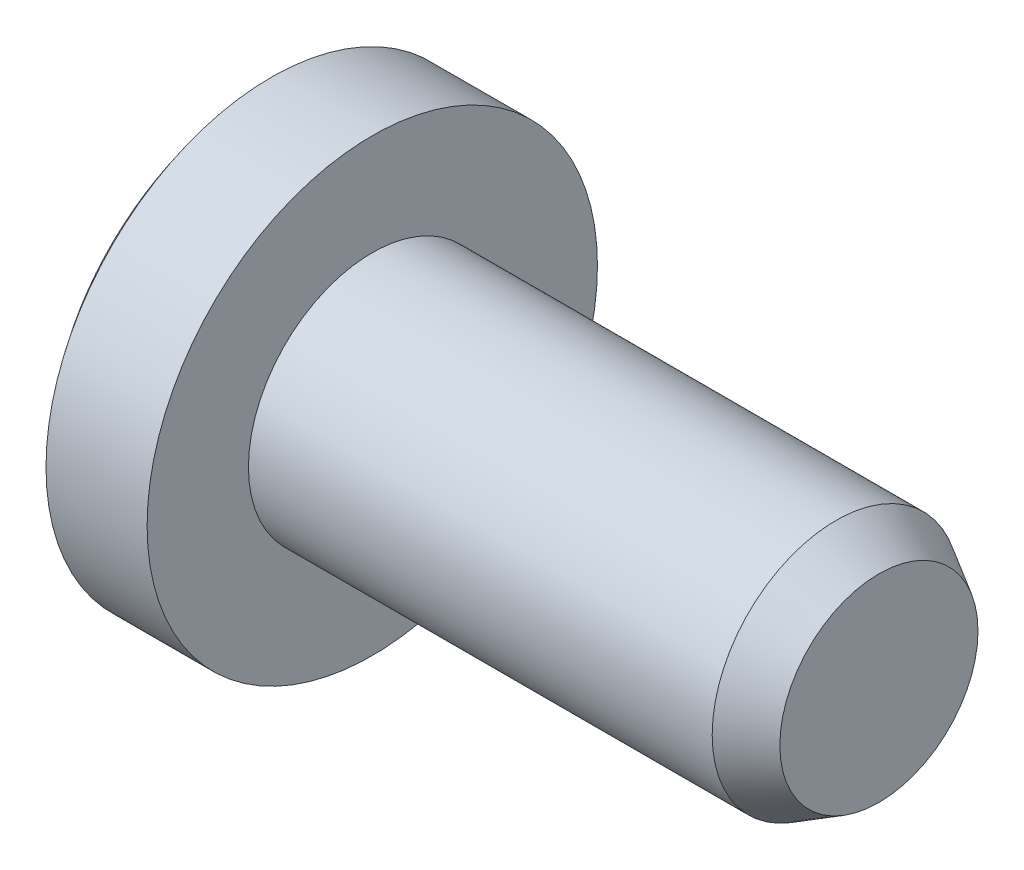
SolidWorks part; units mm, degrees
ref_plane "Front Plane" through (0, 0, 0) normal (0, 0, 1) x (1, 0, 0)
ref_plane "Top Plane" through (0, 0, 0) normal (0, 1, 0) x (1, 0, 0)
ref_plane "Right Plane" through (0, 0, 0) normal (1, 0, 0) x (0, 0, -1)
sketch "Sketch1" plane through (0, 0, 0) normal (0, 0, 1) x (1, 0, 0)
  line L0 (0, 0) -> (5.2282, 0) construction
  line L2 (0, 2) -> (-0.898, 2)
  line L3 (-1.6, 0) -> (-1.6, -0.7496) construction
  line L4 (-1.6, 0) -> (4.5, 0)
  line L5 (0, 1.1) -> (4.5, 1.1)
  line L6 (4.5, 1.1) -> (4.5, 0)
  line L7 (0, 1.1) -> (0, 2)
  arc A0 (-0.898, 2) -> (-1.6, 0) centre (1.6, 0) ccw
  dimension "l" = 4.5
revolve "Revolve1" add sketch "Sketch1" angle 360 about L0
cosmetic thread "ThreadCosmetic" [suppressed] parameters "D1"=4.28, "D2"=1.65
chamfer "Chamfer1" distance 0.22 angle 60 1 edges at (4.5, 0, 1.1) first distance on face at (4.5, 0, 1.1)
sketch "Sketch5" plane through (0, 0, 0) normal (0, 0, 1) x (1, 0, 0)
  line L0 (0.3703, 0.825) -> (0.2069, 0.825)
  line L1 (0.2069, 0.825) -> (0.0481, 1.1)
  line L2 (0.3703, 0.825) -> (0.529, 1.1)
  line L3 (0.0481, 1.1) -> (0.0481, 1.35)
  line L4 (0.529, 1.1) -> (0.529, 1.35)
  line L5 (0.0481, 1.35) -> (0.529, 1.35)
  line L6 (0.2886, 0.825) -> (0.2886, 0) construction
  line L7 (0, 0) -> (7.3035, 0) construction
  line L9 (4.1189, 1.1) -> (0, 1.1) construction
  line L12 (0, -1.1) -> (0, 1.1) construction
  dimension "D2" = 60
  dimension "D3" = 0.25
  dimension "minordia" = 1.65
  dimension "threadstart" = 0.2886
revolve "ThreadSchematic" [suppressed] cut sketch "Sketch5" angle 360 about L7
pattern_linear "ThdSchPat" [suppressed] count 10 spacing 0.4809 along (1, 0, 0) of bodies 105
sketch "Sketch2" plane through (0, 0, 0) normal (0, 0, 1) x (1, 0, 0)
  line L0 (0, 0) -> (5.7679, 0) construction
  line L1 (4.5, 0) -> (2.5947, 1.1)
  line L3 (4.5, 1.1) -> (4.5, 0) construction
  line L4 (2.5947, 1.1) -> (2.5947, 1.2)
  line L5 (2.5947, 1.2) -> (4.6, 1.2)
  line L6 (4.6, 1.2) -> (4.6, 0)
  line L7 (4.6, 0) -> (4.5, 0)
  point P9 (0, 1.1)
  dimension "D1" = 30
  dimension "D2" = 0.1
  dimension "D3" = 0.1
revolve "EndCone" [suppressed] cut sketch "Sketch2" angle 360 about L0
ref_plane "Plane4" through (-1.6, 0, 0) normal (1, 0, 0) x (0, 0, -1)
sketch "Sketch3" plane through (-1.6, 0, 0) normal (1, 0, 0) x (0, 0, -1)
  line L0 (0, 2.343) -> (0, -2.4842) construction
  line L1 (2.7661, 0) -> (-3.4558, 0) construction
  line L2 (-0.2375, 0.95) -> (0.2375, 0.95)
  line L3 (0.2375, 0.95) -> (0.1425, 0.57)
  line L4 (0, 0) -> (1.9578, 1.9578) construction
  line L5 (0.1425, 0.57) -> (0.299, 0.299)
  line L6 (0.1425, 0.57) -> (0, 0) construction
  line L7 (-0.1425, 0.57) -> (-0.299, 0.299)
  line L8 (-0.2375, 0.95) -> (-0.1425, 0.57)
  line L9 (0.95, 0.2375) -> (0.95, -0.2375)
  line L10 (0.95, -0.2375) -> (0.57, -0.1425)
  line L11 (0.57, -0.1425) -> (0.299, -0.299)
  line L12 (0.57, 0.1425) -> (0.299, 0.299)
  line L13 (0.95, 0.2375) -> (0.57, 0.1425)
  line L14 (0.2375, -0.95) -> (-0.2375, -0.95)
  line L15 (-0.2375, -0.95) -> (-0.1425, -0.57)
  line L16 (-0.1425, -0.57) -> (-0.299, -0.299)
  line L17 (0.1425, -0.57) -> (0.299, -0.299)
  line L18 (0.2375, -0.95) -> (0.1425, -0.57)
  line L19 (-0.95, -0.2375) -> (-0.95, 0.2375)
  line L20 (-0.95, 0.2375) -> (-0.57, 0.1425)
  line L21 (-0.57, 0.1425) -> (-0.299, 0.299)
  line L22 (-0.57, -0.1425) -> (-0.299, -0.299)
  line L23 (-0.95, -0.2375) -> (-0.57, -0.1425)
  point P14 (0, 0.95)
  point P23 (0.95, 0)
  point P30 (0, -0.95)
  point P37 (-0.95, 0)
  dimension "D1" = 45
  dimension "D3" = 0.475
  dimension "D4" = 75
  dimension "D5" = 1.14
  dimension "m" = 1.9
extrude "Cut-Extrude1" cut sketch "Sketch3" along normal blind 0.8 draft 6
sketch "Sketch4" plane through (-1.6, 0, 0) normal (1, 0, 0) x (0, 0, -1)
  line L0 (0, 2.1951) -> (0, -2.1951) construction
  line L1 (2.1996, 0) -> (-2.3835, 0) construction
  line L2 (-0.8397, -0.8397) -> (0.8397, 0.8397) construction
  line L3 (0.95, 0.2375) -> (-0.95, 0.2375)
  line L4 (0.95, 0.2375) -> (0.95, -0.2375)
  line L5 (0.95, -0.2375) -> (-0.95, -0.2375)
  line L6 (-0.95, 0.2375) -> (-0.95, -0.2375)
  line L7 (0.2375, 0.95) -> (-0.2375, 0.95)
  line L8 (0.2375, 0.95) -> (0.2375, -0.95)
  line L9 (0.2375, -0.95) -> (-0.2375, -0.95)
  line L10 (-0.2375, 0.95) -> (-0.2375, -0.95)
  line L11 (0.8397, 0.8397) -> (0.3859, 0.2375)
  line L12 (0.8397, 0.8397) -> (0.2375, 0.3859)
  line L13 (0.2375, 0.3859) -> (-0.2375, 0.3859) construction
  line L14 (0, 0) -> (-0.8397, 0.8397) construction
  line L15 (-0.8397, -0.8397) -> (-0.2375, -0.3859)
  line L16 (-0.8397, -0.8397) -> (-0.3859, -0.2375)
  line L17 (-0.2375, 0.3859) -> (-0.8397, 0.8397)
  line L18 (-0.8397, 0.8397) -> (-0.3859, 0.2375)
  line L19 (-0.3859, -0.2375) -> (-0.3859, 0.2375) construction
  line L20 (0.3859, -0.2375) -> (0.8397, -0.8397)
  line L21 (0.8397, -0.8397) -> (0.2375, -0.3859)
  circle A0 centre (0, 0) radius 1.1875 construction
  dimension "D1" = 2.375
  dimension "D2" = 0.475
  dimension "m" = 1.9
  dimension "D3" = 45
  dimension "D4" = 8
  dimension "D5" = 45
extrude "TypeZ" [suppressed] cut sketch "Sketch4" along normal blind 0.8
equation "\"D1@Chamfer1\" = \"d@Sketch1\"/10"
equation "\"D1@ThreadCosmetic\" = \"l@Sketch1\" - \"D1@Chamfer1\""
equation "\"minordia@Sketch5\" = \"D2@ThreadCosmetic\""
equation "\"D1@Plane4\" = \"K@Sketch1\""
equation "\"D5@Sketch3\" = \"m@Sketch3\" * 3 / 5"
equation "\"D3@Sketch3\" = \"m@Sketch3\" / 4"
equation "\"D2@Sketch4\" =  \"m@Sketch4\" / 4"
equation "\"D1@TypeZ\" = \"K@Sketch1\" / 2"
equation "\"D1@Sketch4\" = \"m@Sketch4\" * 5 / 4"
equation "\"m@Sketch4\" = \"m@Sketch3\""
equation "\"threadstart@Sketch5\" = \"advance@Sketch5\"*0.6"
equation "\"D1@ThdSchPat\" = int((\"l@Sketch1\"/\"advance@Sketch5\") + 0.999)"
equation "\"D3@ThdSchPat\" = \"advance@Sketch5\""
